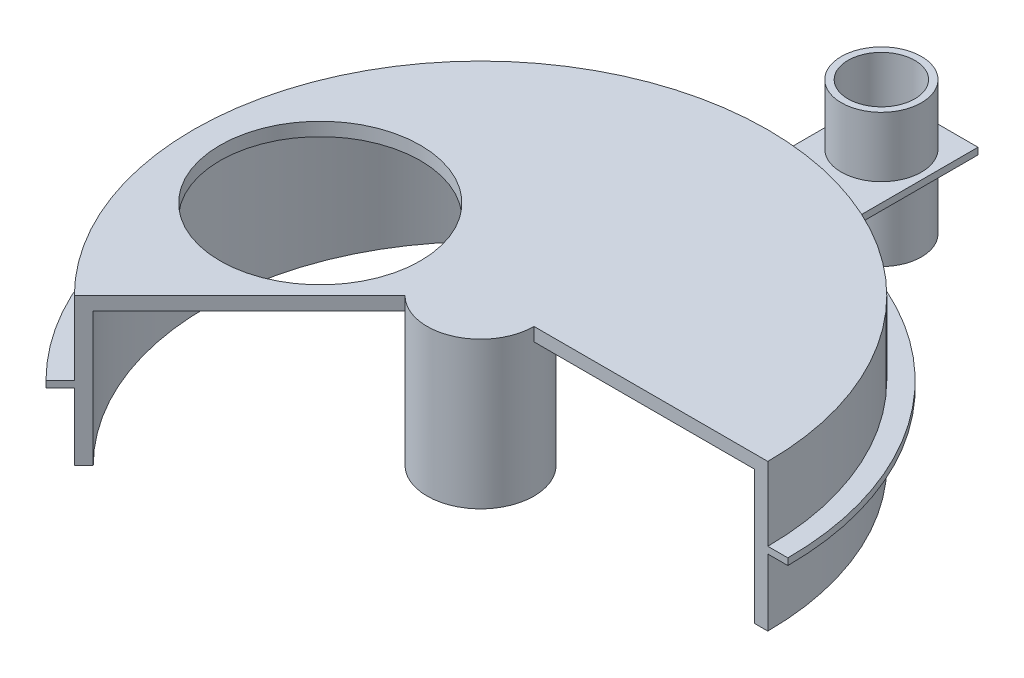
SolidWorks part; units mm, degrees
ref_plane "Alzado" through (0, 0, 0) normal (0, 0, 1) x (1, 0, 0)
ref_plane "Planta" through (0, 0, 0) normal (0, 1, 0) x (1, 0, 0)
ref_plane "Vista lateral" through (0, 0, 0) normal (1, 0, 0) x (0, 0, -1)
sketch "Croquis1" plane through (0, 0, 0) normal (0, 1, 0) x (1, 0, 0)
  circle A0 centre (0, 0) radius 35
  circle A1 centre (0, 0) radius 40
  dimension "D1" = 70
  dimension "D2" = 80
extrude "Saliente-Extruir1" add sketch "Croquis1" along normal blind 100
sketch "Croquis2" plane through (0, 0, 0) normal (0, 1, 0) x (1, 0, 0)
  line L0 (0, 0) -> (-120, 0) construction
  line L1 (0, 0) -> (0, 300) construction
  line L3 (215, 0) -> (205, 0)
  line L4 (0, 0) -> (-144.9569, -144.9569) construction
  line L5 (0, 0) -> (-152.028, -152.028) construction
  line L6 (-144.9569, -144.9569) -> (-152.028, -152.028)
  circle A0 centre (0, 0) radius 120 construction
  circle A1 centre (-120, 0) radius 50 construction
  circle A2 centre (0, 0) radius 205 construction
  circle A3 centre (0, 300) radius 25
  circle A4 centre (0, 0) radius 215 construction
  arc A5 (-215, 0) -> (215, 0) centre (0, 0) cw
  arc A6 (205, 0) -> (-205, 0) centre (0, 0) ccw
  circle A7 centre (0, 300) radius 30
  circle A8 centre (120, 0) radius 50 construction
  arc A9 (-215, 0) -> (-152.028, -152.028) centre (0, 0) ccw
  arc A10 (-205, 0) -> (-144.9569, -144.9569) centre (0, 0) ccw
  dimension "D1" = 240
  dimension "D2" = 100
  dimension "D3" = 410
  dimension "D5" = 50
  dimension "D6" = 430
  dimension "D7" = 60
  dimension "D8" = 100
  dimension "D9" = 45
  dimension "D4" = 300
  dimension "D10" = 45
extrude "Saliente-Extruir2" add sketch "Croquis2" along normal blind 100 separate body
sketch "Croquis3" plane through (0, 100, 0) normal (0, 1, 0) x (1, 0, 0)
  line L0 (-152.028, -152.028) -> (-144.9569, -144.9569) construction
  line L1 (-152.028, -152.028) -> (0, 0)
  line L2 (0, 0) -> (215, 0)
  arc A0 (215, 0) -> (-152.028, -152.028) centre (0, 0) ccw
  circle A1 centre (0, 0) radius 120 construction
  circle A2 centre (-120, 0) radius 75
  arc M1 (215, 0) -> (-152.028, -152.028) centre (0, 0) ccw
  arc M3 (-144.9569, -144.9569) -> (205, 0) centre (0, 0) cw
  line M4 (205, 0) -> (215, 0)
  dimension "D1" = 240
  dimension "D2" = 150
extrude "Saliente-Extruir3" add sketch "Croquis3" along normal blind 10 contours M4 M1 M3 | M3 | A1 | L2 A0 L1 | A2 region at (-80.1135, 100, -193.411) region at (1.3875, 100, -75.6011)
ref_plane "Plano1" through (0, 50, 0) normal (0, 1, 0) x (1, 0, 0)
sketch "Croquis6" plane through (0, 50, 0) normal (0, 1, 0) x (1, 0, 0)
  line L0 (-152.028, -152.028) -> (-162.6346, -162.6346)
  line L1 (-152.028, -152.028) -> (0, 0) construction
  line L2 (-152.028, -152.028) -> (0, 0)
  line L3 (0, 0) -> (215, 0) construction
  line L4 (0, 0) -> (215, 0)
  line L5 (215, 0) -> (230, 0)
  line L6 (-35, 337.3214) -> (35, 337.3214)
  line L7 (-35, 157.5614) -> (35, 157.5614) construction
  line L8 (-35, 157.5614) -> (-35, 337.3214) construction
  line L9 (-35, 337.3214) -> (35, 337.3214) construction
  line L10 (35, 157.5614) -> (35, 337.3214) construction
  line L11 (-35, 157.5614) -> (35, 337.3214) construction
  line L12 (-35, 337.3214) -> (35, 157.5614) construction
  line L13 (35, 337.3214) -> (35, 227.3214)
  line L14 (35, 227.3214) -> (-35, 227.3214)
  line L15 (-35, 227.3214) -> (-35, 337.3214)
  arc A0 (215, 0) -> (-152.028, -152.028) centre (0, 0) ccw construction
  arc A1 (215, 0) -> (-152.028, -152.028) centre (0, 0) ccw
  arc A2 (230, 0) -> (-162.6346, -162.6346) centre (0, 0) ccw
  point P5 (0, 247.4414)
  dimension "D1" = 230
  dimension "D2" = 70
  dimension "D3" = 110
extrude "Saliente-Extruir9" add sketch "Croquis6" along normal blind 5 contours L5 A2 L0 A1 | L15 L6 L13 L14 region at (-161.5954, 50, 153.0671)
sketch "Croquis8" plane through (0, 100, 0) normal (0, 1, 0) x (1, 0, 0)
  line L0 (0, 0) -> (215, 0) construction
  line L1 (0, 0) -> (215, 0) construction
  line L3 (0, 0) -> (-28.2843, -28.2843)
  line L4 (0, 0) -> (40, 0)
  arc A0 (40, 0) -> (-28.2843, -28.2843) centre (0, 0) cw
  line M2 (40, 0) -> (35, 0)
  arc M3 (35, 0) -> (-24.7487, -24.7487) centre (0, 0) cw
  line M4 (-24.7487, -24.7487) -> (-28.2843, -28.2843)
  arc M5 (-28.2843, -28.2843) -> (40, 0) centre (0, 0) ccw
extrude "Saliente-Extruir11" add sketch "Croquis8" along normal blind 10 contours M5 M2 M3 M4 | L4 L3 M3 region at (7.0025, 100, 16.9054) region at (13.6968, 100, 33.0669)
